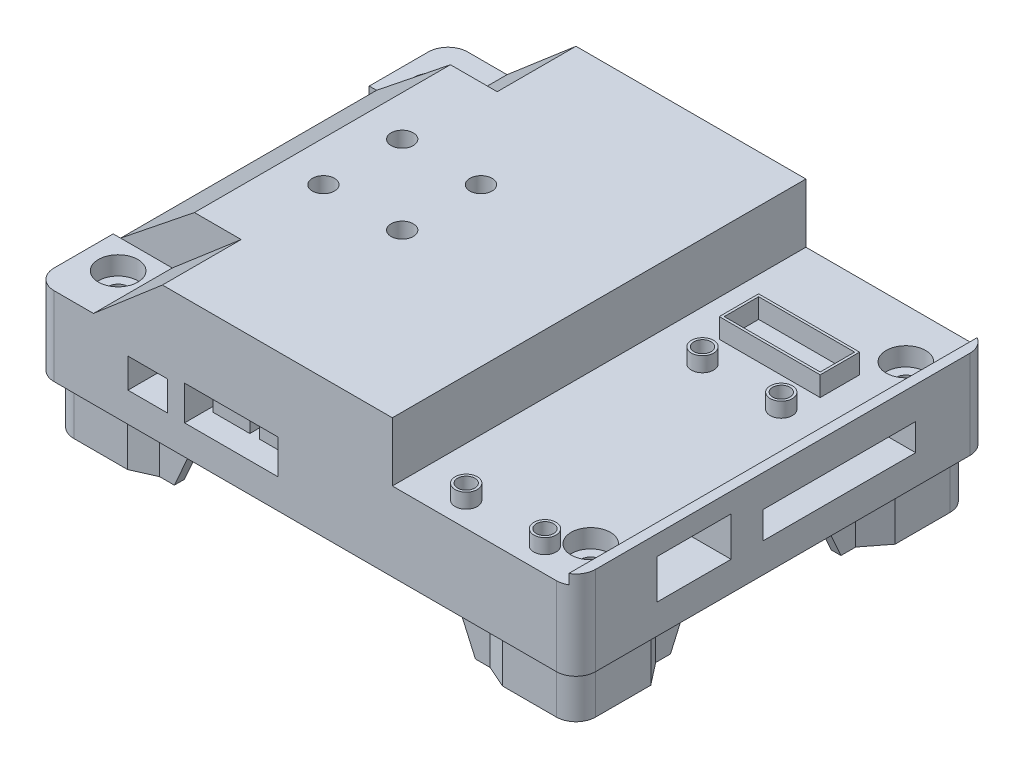
SolidWorks part; units mm, degrees
note: The reader was unsure of these and kept them because the rebuilt part matched: shared geometry of "草图11<2>".
ref_plane "前视基准面" through (0, 0, 0) normal (0, 0, 1) x (1, 0, 0)
ref_plane "上视基准面" through (0, 0, 0) normal (0, 1, 0) x (1, 0, 0)
ref_plane "右视基准面" through (0, 0, 0) normal (1, 0, 0) x (0, 0, -1)
other "Configuration Table"
sketch "草图1" plane through (0, 0, 0) normal (0, 1, 0) x (1, 0, 0)
  line L1 (-55, -42) -> (55, -42)
  line L2 (-55, -42) -> (-55, 42)
  line L3 (-55, 42) -> (55, 42)
  line L4 (55, -42) -> (55, 42)
  line L5 (-55, -42) -> (55, 42) construction
  line L6 (-55, 42) -> (55, -42) construction
  point P0 (0, 0)
  dimension "D1" = 84
  dimension "D2" = 110
extrude "凸台-拉伸1" add sketch "草图1" along normal blind 28
sketch "草图2" plane through (0, 0, 42) normal (0, 0, 1) x (1, 0, 0)
  line L0 (-55, 16) -> (-43, 16)
  line L1 (-55, 28) -> (-55, 0) construction
  line L2 (-43, 16) -> (-29, 28)
  line L3 (-55, 28) -> (55, 28) construction
  line L4 (-29, 28) -> (17.7, 28)
  line L5 (17.7, 28) -> (17.7, 16)
  line L9 (55, 38.9932) -> (-55, 38.9932)
  line L10 (-55, 38.9932) -> (-55, 16)
  line L11 (17.7, 16) -> (53, 16)
  line L12 (53, 16) -> (53, 18)
  line L13 (53, 18) -> (55, 18)
  line L14 (55, 28) -> (55, 0) construction
  line L15 (55, 18) -> (55, 38.9932)
  line L16 (-55, 0) -> (55, 0) construction
  point P18 (-55, 27.4966)
  dimension "D1" = 2
  dimension "D2" = 16
  dimension "D3" = 37.3
  dimension "D4" = 2
  dimension "D5" = 12
  dimension "D6" = 14
extrude "切除-拉伸1" cut sketch "草图2" against normal through all
sketch "草图3" plane through (0, 0, 0) normal (0, 0, 1) x (1, 0, 0)
  line L0 (-53.5, 16) -> (-38.5, 28)
  line L1 (-38.5, 28) -> (-29, 28)
  line L2 (-29, 28) -> (-43, 16)
  line L3 (-43, 16) -> (-53.5, 16)
  line L4 (-29, 28) -> (17.7, 28) construction
  line L5 (-55, 16) -> (-43, 16) construction
  line L6 (-55, 16) -> (-55, 0) construction
  dimension "D1" = 1.5
  dimension "D2" = 15
ref_plane "基准面1" through (-29, 28, 42) normal (1, 0, 0) x (0, 0, -1)
extrude "凸台-拉伸2" add sketch "草图3" along normal mid plane 52
sketch "草图4" plane through (0, 16, 0) normal (0, 1, 0) x (1, 0, 0)
  line L0 (0, 0) -> (53, 0) construction
  line L1 (53, 42) -> (53, -42) construction
  line L2 (0, 0) -> (0, 42) construction
  line L3 (17.7, 42) -> (-29, 42) construction
  line L4 (-55, 42) -> (-55, -42) construction
  line L5 (-53.5, 26) -> (-55, 26)
  line L6 (-53.5, 26) -> (-53.5, -26)
  line L7 (-53.5, -26) -> (-55, -26)
  line L8 (-55, 26) -> (-55, -26)
  line L9 (-53.5, 26) -> (-55, -26) construction
  line L10 (-53.5, -26) -> (-55, 26) construction
  line L11 (-53.5, -26) -> (-43, -26) construction
  circle A0 centre (-48, 32) radius 2
  circle A4 centre (48, 32) radius 2
  circle A5 centre (-48, -32) radius 2
  circle A6 centre (48, -32) radius 2
  point P20 (-54.25, 0)
  dimension "D1" = 4
  dimension "D2" = 96
  dimension "D3" = 64
extrude "切除-拉伸2" cut sketch "草图4" against normal through all
sketch "草图6" plane through (0, 0, 0) normal (0, -1, 0) x (-1, 0, 0)
  line L0 (47.5, 0) -> (47.5, -21)
  line L1 (47.5, -21) -> (51, -25.5)
  line L2 (51, -25.5) -> (51, -38)
  line L3 (51, -38) -> (38.5, -38)
  line L4 (38.5, -38) -> (34, -36)
  line L5 (34, -36) -> (0, -36)
  line L6 (53.5, -26) -> (53.5, 26) construction
  line L7 (55, -42) -> (-55, -42) construction
  circle A0 centre (48, -32) radius 2 construction
  dimension "D3" = 3
  dimension "D4" = 6
  dimension "D1" = 6
  dimension "D2" = 6
  dimension "D5" = 17
  dimension "D6" = 12.5
  dimension "D7" = 17
  dimension "D8" = 12.5
extrude "拉伸-薄壁1" add sketch "草图6" along normal blind 10 thin thin type one direction reverse wall 2
sketch "草图7" plane through (0, 0, 0) normal (0, -1, 0) x (1, 0, 0)
  line L1 (-48, 35) -> (-51, 35)
  line L2 (-51, 25.5) -> (-51, 38) construction
  line L3 (-51, 35) -> (-51, 29)
  line L4 (-51, 29) -> (-48, 29)
  line L5 (-51, 25.5) -> (-51, 38) construction
  circle A0 centre (-48, 32) radius 2
  arc A1 (-48, 29) -> (-48, 35) centre (-48, 32) ccw
  dimension "D1" = 4
extrude "凸台-拉伸5" add sketch "草图7" along normal blind 10
sketch "草图8" plane through (0, 0, 0) normal (0, -1, 0) x (1, 0, 0)
  line L0 (0, 0) -> (0, 36) construction
  line L1 (0, 0) -> (-47.5, 0) construction
mirror "镜向1" about plane through (0, 0, 0) normal (1, 0, 0) of "拉伸-薄壁1", "凸台-拉伸5" second plane through (0, 0, 0) second plane normal (0, 0, 1)
sketch "草图9" plane through (0, 0, -38) normal (0, 0, -1) x (-1, 0, 0)
  line L0 (-30.5756, -10) -> (-26.5756, -1)
  line L1 (33.5756, -10) -> (-33.5756, -10) construction
  line L2 (-26.5756, -1) -> (26.5756, -1)
  line L3 (26.5756, -1) -> (30.5756, -10)
  line L4 (30.5756, -10) -> (-30.5756, -10)
  line L5 (-33.5756, -10) -> (-33.5756, 0) construction
  line L6 (33.5756, -10) -> (33.5756, 0) construction
  line L7 (0, 0) -> (47.5, 0) construction
  dimension "D1" = 4
  dimension "D2" = 4
  dimension "D3" = 3
  dimension "D4" = 3
  dimension "D5" = 1
extrude "切除-拉伸3" cut sketch "草图9" against normal through all
sketch "草图10" plane through (-49.5, 0, 0) normal (-1, 0, 0) x (0, 0, 1)
  line L0 (-17.3138, -10) -> (-13.3138, -1)
  line L1 (-20.3138, -10) -> (20.3138, -10) construction
  line L2 (-13.3138, -1) -> (13.3138, -1)
  line L3 (13.3138, -1) -> (17.3138, -10)
  line L4 (17.3138, -10) -> (-17.3138, -10)
  line L5 (-20.3138, -10) -> (-20.3138, 0) construction
  line L6 (0, 0) -> (36, 0) construction
  dimension "D1" = 3
  dimension "D2" = 3
  dimension "D3" = 1
  dimension "D4" = 4
  dimension "D5" = 4
extrude "切除-拉伸4" cut sketch "草图10" against normal through all
fillet "圆角1" radius 4 12 edges at (-53, -5, 40) (-53, -5, -40) (55, 9, 42) (-55, 8, 42) (-55, 8, -42) (53, -5, 40) (55, 9, -42) (53, -5, -40) (53, 17, 42) (54, 18, 42) (54, 18, -42) (53, 17, -42)
sketch "草图11" plane through (0, 0, 42) normal (0, 0, 1) x (1, 0, 0)
  line L0 (-51, 0) -> (51, 0) construction
  line L1 (-36, 12) -> (-28, 12)
  line L2 (-36, 12) -> (-36, 6)
  line L3 (-36, 6) -> (-28, 6)
  line L4 (-28, 12) -> (-28, 6)
  line L5 (-36, 12) -> (-28, 6) construction
  line L6 (-36, 6) -> (-28, 12) construction
  line L7 (-24.5, 6) -> (-5.5, 6)
  line L8 (-24.5, 6) -> (-24.5, 13)
  line L9 (-24.5, 13) -> (-5.5, 13)
  line L10 (-5.5, 6) -> (-5.5, 13)
  line L11 (-24.5, 6) -> (-5.5, 13) construction
  line L12 (-24.5, 13) -> (-5.5, 6) construction
  line L13 (-55, 0) -> (-55, 16) construction
  point P4 (-32, 9)
  point P9 (-15, 9.5)
  point P14 (-28, 9)
  dimension "D1" = 7
  dimension "D2" = 6
  dimension "D3" = 6
  dimension "D4" = 19
  dimension "D5" = 8
  dimension "D6" = 3.5
  dimension "D7" = 19
extrude "切除-拉伸5" cut sketch "草图11" against normal blind 10
sketch "草图12" plane through (0, 6, 0) normal (0, 1, 0) x (1, 0, 0)
  line L0 (-34, -36) -> (34, -36) construction
  line L1 (-23.5, -34.75) -> (-16, -34.75)
  line L2 (-23.5, -34.75) -> (-23.5, -37.25)
  line L3 (-23.5, -37.25) -> (-16, -37.25)
  line L4 (-16, -34.75) -> (-16, -37.25)
  line L5 (-23.5, -34.75) -> (-16, -37.25) construction
  line L6 (-23.5, -37.25) -> (-16, -34.75) construction
  line L7 (-14, -34.75) -> (-6.5, -34.75)
  line L8 (-14, -34.75) -> (-14, -37.25)
  line L9 (-14, -37.25) -> (-6.5, -37.25)
  line L10 (-6.5, -34.75) -> (-6.5, -37.25)
  line L11 (-14, -34.75) -> (-6.5, -37.25) construction
  line L12 (-14, -37.25) -> (-6.5, -34.75) construction
  line L13 (-24.5, -32) -> (-24.5, -42) construction
  point P4 (-19.75, -36)
  point P9 (-10.25, -36)
  dimension "D1" = 2.5
  dimension "D2" = 2.5
  dimension "D3" = 7.5
  dimension "D4" = 7.5
  dimension "D5" = 2
  dimension "D6" = 1
extrude "凸台-拉伸6" add sketch "草图12" along normal blind 6
extrude "切除-拉伸6" cut sketch "草图11<2>" along normal blind 10 from surface at -84 starting at face at (-4.575, 15, -42)
sketch "草图11<2>" plane through (0, 0, 42) normal (0, 0, 1) x (1, 0, 0) same geometry as "草图11"
sketch "草图14" plane through (55, 0, 0) normal (1, 0, 0) x (0, 0, -1)
  line L1 (-25.5, 6) -> (-10.5, 6)
  line L2 (-25.5, 6) -> (-25.5, 14)
  line L3 (-25.5, 14) -> (-10.5, 14)
  line L4 (-10.5, 6) -> (-10.5, 14)
  line L5 (-25.5, 6) -> (-10.5, 14) construction
  line L6 (-25.5, 14) -> (-10.5, 6) construction
  line L7 (-4, 6) -> (27, 6)
  line L8 (-4, 6) -> (-4, 11.5)
  line L9 (-4, 11.5) -> (27, 11.5)
  line L10 (27, 6) -> (27, 11.5)
  line L11 (-4, 6) -> (27, 11.5) construction
  line L12 (-4, 11.5) -> (27, 6) construction
  line L13 (42, 28) -> (42, 16) construction
  line L14 (-42, 0) -> (-42, 16) construction
  line L15 (-38, 0) -> (38, 0) construction
  point P4 (-18, 10)
  point P9 (11.5, 8.75)
  dimension "D1" = 15
  dimension "D2" = 31
  dimension "D3" = 16.5
  dimension "D4" = 15
  dimension "D5" = 5.5
  dimension "D6" = 8
  dimension "D7" = 6
extrude "切除-拉伸7" cut sketch "草图14" against normal blind 10
sketch "草图15" plane through (0, 16, 0) normal (0, 1, 0) x (1, 0, 0)
  line L0 (17.7, 42) -> (51, 42) construction
  line L1 (25.1, 25) -> (45.6, 25)
  line L2 (25.1, 25) -> (25.1, 17)
  line L3 (25.1, 17) -> (45.6, 17)
  line L4 (45.6, 25) -> (45.6, 17)
  line L5 (25.1, 25) -> (45.6, 17) construction
  line L6 (25.1, 17) -> (45.6, 25) construction
  line L7 (53, 0) -> (17.7, 0) construction
  line L8 (53, 41.4641) -> (53, -41.4641) construction
  line L9 (17.7, 42) -> (17.7, -42) construction
  line L10 (35.35, 0) -> (35.35, 42) construction
  point P4 (35.35, 21)
  dimension "D1" = 17
  dimension "D2" = 8
  dimension "D3" = 20.5
extrude "拉伸-薄壁3" add sketch "草图15" along normal blind 4 thin
sketch "草图16" plane through (0, 16, 0) normal (0, 1, 0) x (1, 0, 0)
  line L0 (17.7, 42) -> (17.7, -42) construction
  line L1 (17.7, -42) -> (51, -42) construction
  circle A0 centre (27.7, 11) radius 2.25
  circle A1 centre (43.7, 11) radius 2.25
  circle A2 centre (27.7, -37) radius 2.25
  circle A3 centre (43.7, -37) radius 2.25
  dimension "D1" = 4.5
  dimension "D2" = 4.5
  dimension "D3" = 4.5
  dimension "D4" = 4.5
  dimension "D5" = 10
  dimension "D6" = 16
  dimension "D7" = 48
  dimension "D8" = 5
extrude "拉伸-薄壁4" add sketch "草图16" along normal blind 3 thin thin type one direction reverse wall 0.5
sketch "草图17" plane through (0, 16, 0) normal (0, 1, 0) x (1, 0, 0)
  circle A0 centre (48, 32) radius 4
  circle A1 centre (48, -32) radius 4
  circle A2 centre (-48, -32) radius 4
  circle A3 centre (-48, 32) radius 4
  circle A4 centre (-48, 32) radius 2 construction
  dimension "D1" = 8
  dimension "D2" = 8
  dimension "D3" = 8
  dimension "D4" = 8
extrude "切除-拉伸8" cut sketch "草图17" against normal blind 3.75
sketch "草图18" plane through (0, 28, 0) normal (0, 1, 0) x (1, 0, 0)
  line L0 (-30.3, 8) -> (-14.3, -8) construction
  line L1 (-14.3, 8) -> (-30.3, -8) construction
  line L2 (17.7, 42) -> (17.7, -42) construction
  circle A0 centre (-30.3, 8) radius 2.25
  circle A1 centre (-14.3, 8) radius 2.25
  circle A2 centre (-30.3, -8) radius 2.25
  circle A3 centre (-14.3, -8) radius 2.25
  point P9 (-22.3, 0)
  point P14 (17.7, 0)
  dimension "D1" = 4.5
  dimension "D2" = 4.5
  dimension "D3" = 4.5
  dimension "D4" = 4.5
  dimension "D6" = 16
  dimension "D5" = 16
  dimension "D7" = 40
extrude "切除-拉伸9" cut sketch "草图18" against normal blind 8
equation "\"D2@草图16\"=\"D1@草图16\""
equation "\"D3@草图16\"=\"D1@草图16\""
equation "\"D4@草图16\"=\"D1@草图16\""
equation "\"D2@草图17\"=\"D1@草图17\""
equation "\"D3@草图17\"=\"D1@草图17\""
equation "\"D4@草图17\"=\"D1@草图17\""
equation "\"D2@草图18\"=\"D1@草图18\""
equation "\"D3@草图18\"=\"D1@草图18\""
equation "\"D4@草图18\"=\"D1@草图18\""
